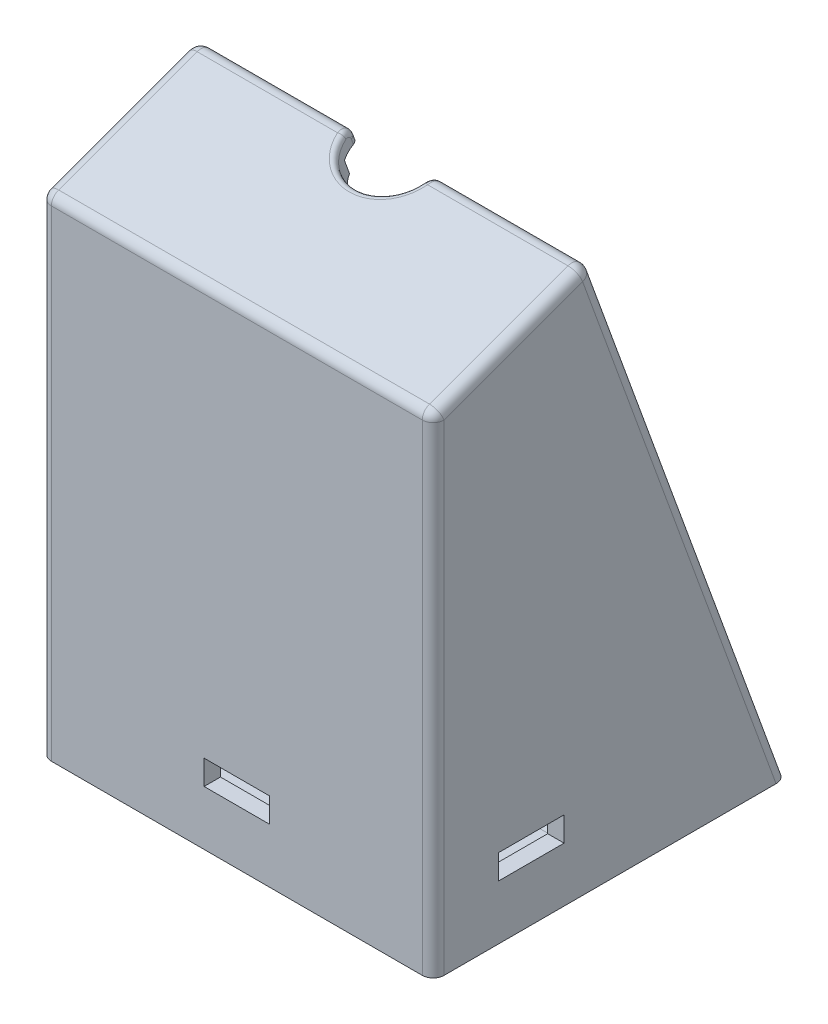
SolidWorks part; units mm, degrees
ref_plane "Front Plane" through (0, 0, 0) normal (0, 0, 1) x (1, 0, 0)
ref_plane "Top Plane" through (0, 0, 0) normal (0, 1, 0) x (1, 0, 0)
ref_plane "Right Plane" through (0, 0, 0) normal (1, 0, 0) x (0, 0, -1)
sketch "Sketch2" plane through (0, 0, 0) normal (1, 0, 0) x (0, 0, -1)
  line L0 (0, 0) -> (-36.397, 100)
  line L1 (0, 0) -> (-65, 0)
  line L4 (-65, 0) -> (-65, 89.5894)
  line L5 (-36.397, 100) -> (-65, 89.5894)
  dimension "D1" = 65
  dimension "D2" = 30.4387
  dimension "D3" = 106.4178
  dimension "D4" = 70
  dimension "D5" = 110
extrude "Boss-Extrude2" add sketch "Sketch2" along normal mid plane 72 contours L0 L5 L4 L1
sketch "Sketch3" plane through (0, 0, 0) normal (0, 0.342, -0.9397) x (-1, 0, 0)
  line L0 (-35.686, 105.9537) -> (27980.4842, -41302.6374) construction
  line L13 (35.686, 105.9537) -> (-27980.4842, -41302.6374) construction
  line L14 (0, 103.3589) -> (0, 106.4178) construction
  line L15 (32.65, 3.0589) -> (-32.65, 3.0589)
  line L16 (32.65, 3.0589) -> (32.65, 103.3589)
  line L17 (32.65, 103.3589) -> (-32.65, 103.3589)
  line L18 (-32.65, 3.0589) -> (-32.65, 103.3589)
  line L19 (32.65, 3.0589) -> (-32.65, 103.3589) construction
  line L20 (32.65, 103.3589) -> (-32.65, 3.0589) construction
  line L21 (-36, 106.4178) -> (36, 106.4178) construction
  point P4 (0, 53.2089)
  point P5 (0, 53.2089)
  dimension "D1" = 100.3
  dimension "D2" = 65.3
extrude "Cut-Extrude1" cut sketch "Sketch3" against normal blind 3.5
ref_plane "Deep Cut plane" through (0, 0, 4.3351) normal (0, 0, -1) x (-1, 0, 0)
shell "Shell1" thickness 3 removed face at (0, 48.8029, 21.4874)
fillet "Fillet1" radius 2 8 edges at (36, 44.7947, 65) (-36, 44.7947, 65) (0, 89.5894, 65) (-36, 50, 18.1985) (-36, 94.7947, 50.6985) (36, 94.7947, 50.6985) (36, 50, 18.1985) (0, 100, 36.397)
sketch "Sketch6" plane through (36, 0, 0) normal (1, 0, 0) x (0, 0, -1)
  line L0 (-2.1284, 0) -> (-63, 0) construction
  line L6 (-63, 88.189) -> (-63, 0) construction
  line L7 (-53, 10) -> (-41, 10)
  line L8 (-53, 10) -> (-53, 14.5)
  line L9 (-53, 14.5) -> (-41, 14.5)
  line L10 (-41, 10) -> (-41, 14.5)
  dimension "D1" = 10
  dimension "D2" = 10
  dimension "D3" = 4.5
  dimension "D4" = 12
extrude "Cut-Extrude2" cut sketch "Sketch6" against normal through all both and the other way through all
sketch "Sketch7" plane through (0, 0, 65) normal (0, 0, 1) x (1, 0, 0)
  line L5 (34, 0) -> (-34, 0) construction
  line L6 (-34, 88.189) -> (-34, 0) construction
  line L7 (-6, 10) -> (6, 10)
  line L8 (-6, 10) -> (-6, 14.5)
  line L9 (-6, 14.5) -> (6, 14.5)
  line L10 (6, 10) -> (6, 14.5)
  line L11 (-6, 10) -> (6, 14.5) construction
  line L12 (-6, 14.5) -> (6, 10) construction
  dimension "D1" = 10
  dimension "D2" = 12
  dimension "D3" = 4.5
  dimension "D4" = 28
extrude "Cut-Extrude3" cut sketch "Sketch7" against normal blind 3.5
sketch "Sketch8" plane through (-33, 0, 0) normal (1, 0, 0) x (0, 0, -1)
  line L3 (-38.6599, 95.9839) -> (-4.8165, 3) construction
  line L5 (-37.6988, 93.3433) -> (-61.9937, 87.491)
  line L8 (-5.3296, 4.4095) -> (-33.9097, 3)
  line L9 (-4.8165, 3) -> (-62, 3) construction
  line L10 (-33.9097, 3) -> (-4.8165, 3)
  line L11 (-5.3296, 4.4095) -> (-4.8165, 3)
  line L12 (-41, 10) -> (-53, 10) construction
  line L13 (-61.9937, 87.491) -> (-38.6599, 95.9839)
  line L14 (-38.6599, 95.9839) -> (-37.6988, 93.3433)
  line M11 (-38.6599, 95.9839) -> (-62, 87.4887)
  dimension "D1" = 28.6149
  dimension "D2" = 1.5
  dimension "D3" = 24.9898
  dimension "D4" = 2.81
extrude "Boss-Extrude3" add sketch "Sketch8" along normal up to surface (66 mm away) contours L5 M11 region at (-33, 92.2727, 46.1175) up to face at (33, 12.25, 47)
extrude "Boss-Extrude4" add sketch "Sketch8<4>" along normal up to surface (66 mm away) contours L11 L8 L10 up to face at (33, 54.8646, 45.7018)
sketch "Sketch8<4>" plane through (-33, 0, 0) normal (1, 0, 0) x (0, 0, -1) same geometry as "Sketch8"
ref_plane "Side Support Plane" through (0, 97.1256, 35.3508) normal (0, -0.9397, -0.342) x (-1, 0, 0)
sketch "Sketch10" plane through (0, 97.1256, 35.3508) normal (0, -0.9397, -0.342) x (-1, 0, 0)
  line L0 (-33, 0) -> (-33, -3.5) construction
  line L4 (-33, -15.5191) -> (-33, -3.5)
  line L5 (0, 0) -> (0, 50000) construction
  line L9 (-33, -3.5) -> (-31, -3.5)
  line L10 (-31, -3.5) -> (-33, -15.5191)
  line L11 (-34, -29.0382) -> (-34, -2) construction
  line L12 (33, -3.5) -> (31, -3.5)
  line L13 (31, -3.5) -> (33, -15.5191)
  line L14 (33, -15.5191) -> (33, -3.5)
  dimension "D1" = 3.5
  dimension "D2" = 2
  dimension "D3" = 1
  dimension "D4" = 15.5191
extrude "Boss-Extrude5" add sketch "Sketch10" along normal up to surface (97.3925 mm away) up to face at (0, 3.9397, 14.8563)
sketch "Sketch12" plane through (0, 97.1256, 35.3508) normal (0, -0.9397, -0.342) x (1, 0, 0)
  line L0 (-32.65, 3.5) -> (-22.65, 3.5)
  line L1 (31, 3.5) -> (-31, 3.5) construction
  line L2 (-22.65, 3.5) -> (-17.65, 3.5)
  line L3 (0, 0) -> (0, 10.5556) construction
  line L4 (-32.65, 0) -> (32.65, 0) construction
  line L5 (0, 10.5556) -> (0, -14.4509) construction
  line L6 (-17.65, 3.5) -> (-17.65, 0)
  line L7 (-17.65, 0) -> (-22.65, 0)
  line L8 (-22.65, 0) -> (-22.65, 3.5)
  line L9 (17.65, 0) -> (22.65, 0)
  line L10 (17.65, 3.5) -> (17.65, 0)
  line L11 (22.65, 3.5) -> (17.65, 3.5)
  line L12 (22.65, 0) -> (22.65, 3.5)
  line L13 (32.65, 3.5) -> (22.65, 3.5)
  line M6 (-32.65, 0) -> (32.65, 0)
  line M8 (32.65, 3.5) -> (-32.65, 3.5)
  dimension "D1" = 5
  dimension "D2" = 10
  dimension "D3" = 10
  dimension "D4" = 5
  dimension "D5" = 35.3
extrude "Upper Support Extrude" add sketch "Sketch12" along normal blind 2.75 contours L8 L6 M6 M8 | L12 L10 M6 M8 region at (-20.15, 96.527, 36.9953) region at (20.15, 96.527, 36.9953)
sketch "Finger Groove sketch" plane through (0, 100, 36.397) normal (0, 0.9397, 0.342) x (1, 0, 0)
  circle A0 centre (0, 0) radius 7.5
  dimension "D1" = 15
extrude "Cut-Extrude4" cut sketch "Finger Groove sketch" against normal up to surface (5.3573 mm away) up to face at (0, 90.4483, 49.7169)
fillet "Fillet2" radius 1 5 edges at (-7.5, 97.6231, 35.5319) (-7.4872, 99.1443, 36.5513) (7.5, 97.6231, 35.5319) (7.4603, 99.3394, 36.9765) (0, 97.4348, 43.4447)
ref_plane "Dovetail Groove Plane" through (0, 5.6066, 2.0406) normal (0, 0.9397, 0.342) x (1, 0, 0)
sketch "Sketch15" plane through (0, 5.6066, 2.0406) normal (0, 0.9397, 0.342) x (1, 0, 0)
  line L0 (-32.65, -3.5) -> (-32.65, 0) construction
  line L2 (-32.65, -3.5) -> (-32.65, 0)
  line L3 (-22.65, -3.5) -> (-24.2821, 0)
  line L4 (-32.65, -3.5) -> (-22.65, -3.5)
  line L5 (32.65, 0) -> (-32.65, 0) construction
  line L6 (-24.2821, 0) -> (-12.2821, 0)
  line L7 (-12.2821, 0) -> (-13.9142, -3.5)
  line L8 (31, -3.5) -> (-31, -3.5) construction
  line L9 (-13.9142, -3.5) -> (-22.65, -3.5)
  line L10 (0, 0) -> (0, 5.0774) construction
  line L11 (32.65, -3.5) -> (22.65, -3.5)
  line L12 (13.9142, -3.5) -> (22.65, -3.5)
  line L13 (12.2821, 0) -> (13.9142, -3.5)
  line L14 (24.2821, 0) -> (12.2821, 0)
  line L15 (22.65, -3.5) -> (24.2821, 0)
  dimension "D1" = 10
  dimension "D2" = 65
  dimension "D3" = 12
  dimension "D4" = 295
extrude "Boss-Extrude8" add sketch "Sketch15" against normal up to surface (2.9075 mm away) contours L12 L15 L14 L13 | L9 L7 L6 L3 region at (-18.2821, 5.0395, 3.5988) region at (18.2821, 5.0395, 3.5988) up to face at (0, 2.2759, 2.6907)
fillet "Fillet3" radius 0.381 11 edges at (-23.466, 2.2759, 2.6907) (-13.0981, 2.2759, 2.6907) (-28.466, 2.8744, 1.0462) (-24.2821, 4.2405, 1.5434) (0, 2.8744, 1.0462) (-12.2821, 4.2405, 1.5434) (12.2821, 4.2405, 1.5434) (28.466, 2.8744, 1.0462) (24.2821, 4.2405, 1.5434) (23.466, 2.2759, 2.6907) (13.0981, 2.2759, 2.6907)
